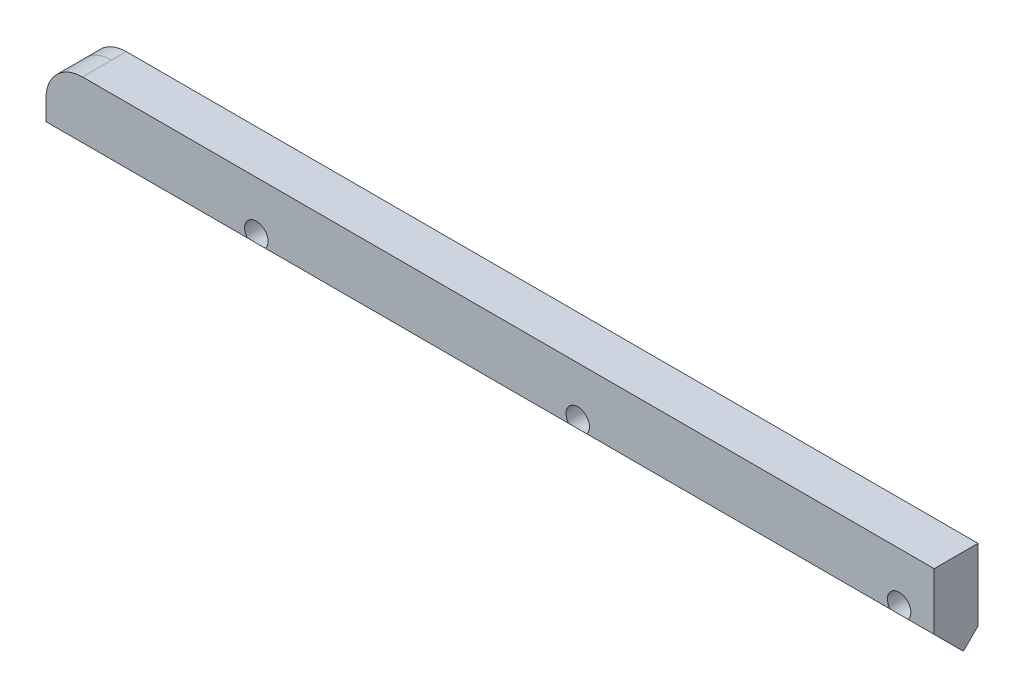
SolidWorks part; units mm, degrees
material "6061-T6 (SS)"
ref_plane "Front Plane" through (0, 0, 0) normal (0, 0, 1) x (1, 0, 0)
ref_plane "Top Plane" through (0, 0, 0) normal (0, 1, 0) x (1, 0, 0)
ref_plane "Right Plane" through (0, 0, 0) normal (1, 0, 0) x (0, 0, -1)
sketch "Sketch1" plane through (0, 0, 0) normal (1, 0, 0) x (0, 0, -1)
  line L0 (-3.0983, 0) -> (1.226, 0) construction
  line L1 (0, -3.2) -> (-2, -1.2)
  line L2 (0, -3.2) -> (0, 3.2)
  line L4 (-2, -1.2) -> (-2, 3.2)
  line L5 (-2, 3.2) -> (0, 3.2)
  dimension "D1" = 2
  dimension "D2" = 45
  dimension "D3" = 6.4
extrude "Boss-Extrude1" add sketch "Sketch1" along normal mid plane 72.8
fillet "Fillet3" radius 2.5 2 edges at (-36.4, 3.2, 1) (36.4, 3.2, 1)
sketch "Sketch5" plane through (-36.4, 0, 0) normal (-1, 0, 0) x (0, 0, 1)
  line L0 (0, -2.7) -> (2, -0.7)
  line L1 (0, -3.2) -> (0, 0.7) construction
  line L2 (2, 0.7) -> (2, -1.2) construction
  line L3 (2, -1.2) -> (0, -3.2) construction
  line L4 (2, -1.2) -> (2, -0.7)
  line L5 (2, -1.2) -> (0, -3.2)
  line L6 (0, -3.2) -> (0, -2.7)
  dimension "D1" = 0.5
extrude "Cut-Extrude5" cut sketch "Sketch5" against normal up to surface (72.8 mm away) up to face at (36.4, -0.75, 1)
sketch "Sketch7" plane through (-36.4, 0, 0) normal (-1, 0, 0) x (0, 0, 1)
  line L0 (0, -2.7) -> (-1, -1.7)
  line L1 (-1, -1.7) -> (-1, 3.2)
  line L2 (-1, 3.2) -> (0, 3.2)
  line L3 (0, 3.2) -> (0, -2.7)
  line L4 (0, 3.2) -> (2, 3.2) construction
  dimension "D1" = 45
  dimension "D2" = 3
extrude "Boss-Extrude2" add sketch "Sketch7" against normal up to surface (72.8 mm away) up to face at (36.4, -0.5, 1)
hole_wizard "M2x0.4 Tapped Hole1" positions "Sketch2" profile "Sketch3" tap size "M2x0.4" standard "ANSI Metric"
sketch "Sketch2" plane through (0, 0, 2) normal (0, 0, 1) x (1, 0, 0)
  circle A4 centre (-22, -0.2) radius 1.2 construction
  circle A5 centre (-22, -0.2) radius 1.2
  circle A8 centre (22, -0.2) radius 1.2 construction
  circle A9 centre (22, -0.2) radius 1.2
  circle A10 centre (0, -0.2) radius 1.2
  point P22 (-22, -0.2)
  point P28 (22, -0.2)
  point P31 (0, -0.2)
cosmetic thread "Hole Thread4" parameters "D1"=3, "D2"=2
cosmetic thread "Hole Thread6" parameters "D1"=3, "D2"=2
sketch "Sketch3" plane through (-22, -0.2, 2) normal (1, 0, 0) x (0, -1, 0)
  line L0 (0, 0) -> (0, 4.0807)
  line L1 (0, 4.0807) -> (0.8, 3.6)
  line L2 (0.8, 3.6) -> (0.8, 0)
  line L5 (0.8, 0) -> (0, 0)
  line L10 (0, 4.0807) -> (-0.8, 3.6) construction
  line L11 (0, -6.35) -> (0, 107.95) construction
  dimension "Tap Drill Dia." = 1.6
  dimension "Tap Drill Depth" = 3.6
  dimension "Drill Angle" = 118
cosmetic thread "Hole Thread7" parameters "D1"=3, "D2"=2
fillet "Fillet4" radius 2.5 2 edges at (-36.4, 3.2, -0.5) (36.4, 3.2, -0.5)
sketch "Sketch4" [suppressed] plane through (0, 0, 0) normal (0, 0, 1) x (1, 0, 0)
  line L1 (7.5, 1.5) -> (-7.5, 1.5)
  line L2 (7.5, 1.5) -> (7.5, -3.2)
  line L3 (7.5, -3.2) -> (-7.5, -3.2)
  line L4 (-7.5, 1.5) -> (-7.5, -3.2)
  line L5 (0, 7.7759) -> (0, -8.8374) construction
  line L8 (-7.5, -1.7) -> (-7.5, -0.7) construction
  dimension "D1" = 4.7
extrude "Cut-Extrude4" [suppressed] cut sketch "Sketch4" along normal mid plane 10
sketch "Sketch8" [suppressed] plane through (36.4, 0, 0) normal (1, 0, 0) x (0, 0, -1)
  line L1 (-1, -3.2) -> (-2, -2.2)
  line L2 (-2, -2.2) -> (-2, -1.2)
  line L3 (-2, -1.2) -> (0, -3.2)
  line L4 (0, -3.2) -> (-1, -3.2)
  dimension "D1" = 1
extrude "Boss-Extrude3" [suppressed] add sketch "Sketch8" against normal blind 3
sketch "Sketch10" [suppressed] plane through (7.5, 0, 0) normal (-1, 0, 0) x (0, 0, 1)
  line L1 (1, -3.2) -> (2, -2.2)
  line L2 (2, -2.2) -> (2, -1.2)
  line L3 (2, -1.2) -> (0, -3.2)
  line L4 (2, -2.2) -> (1, -3.2) construction
  line L5 (0, -3.2) -> (1, -3.2)
extrude "Boss-Extrude5" [suppressed] add sketch "Sketch10" against normal blind 3
mirror "Mirror1" [suppressed] about plane through (0, 0, 0) normal (1, 0, 0)
sketch "Sketch11" [suppressed] plane through (36.4, 0, 0) normal (1, 0, 0) x (0, 0, -1)
  line L0 (0, -2.7) -> (-1, -2.7)
  line L1 (-1, -2.7) -> (-2, -1.7)
  line L2 (-2, -1.7) -> (-2, -0.7)
  line L3 (0, -2.7) -> (-2, -0.7)
  dimension "D1" = 1
extrude "Boss-Extrude6" [suppressed] add sketch "Sketch11" against normal blind 3 separate body
sketch "Sketch12" [suppressed] plane through (7.5, 0, 0) normal (-1, 0, 0) x (0, 0, 1)
  line L0 (0, -2.7) -> (1, -2.7)
  line L1 (1, -2.7) -> (2, -1.7)
  line L2 (2, -1.7) -> (2, -0.7)
  line L3 (0, -2.7) -> (2, -0.7)
  line L4 (1, -2.7) -> (0, -2.7) construction
  line L5 (2, -1.7) -> (1, -2.7) construction
extrude "Boss-Extrude7" [suppressed] add sketch "Sketch12" against normal blind 3
mirror "Mirror7" [suppressed] about plane through (0, 0, 0) normal (1, 0, 0) of bodies 112 111
sketch "Sketch13" plane through (0, 0, 2) normal (0, 0, 1) x (1, 0, 0)
  line L0 (24.4, 3.2) -> (24.4, -2.7)
  line L1 (33.9, 3.2) -> (-33.9, 3.2) construction
  line L2 (36.4, -2.7) -> (-36.4, -2.7) construction
  line L4 (24.4, -2.7) -> (36.4, -2.7)
  line L5 (36.4, -2.7) -> (36.4, 3.2)
  line L6 (36.4, 3.2) -> (24.4, 3.2)
  point P4 (0, 0)
  dimension "D1" = 12
extrude "Cut-Extrude6" cut sketch "Sketch13" against normal up to surface (3 mm away) up to face at (-22.8, -0.2, -1)
